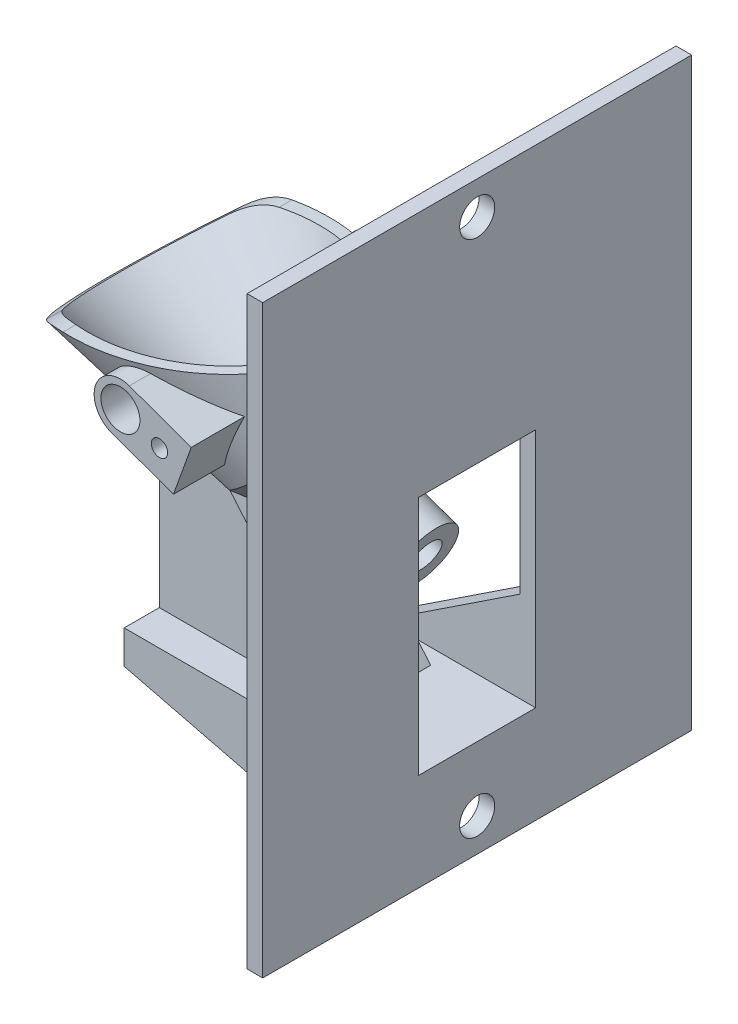
SolidWorks part; units mm, degrees
ref_plane "Front Plane" through (0, 0, 0) normal (0, 0, 1) x (1, 0, 0)
ref_plane "Top Plane" through (0, 0, 0) normal (0, 1, 0) x (1, 0, 0)
ref_plane "Right Plane" through (0, 0, 0) normal (1, 0, 0) x (0, 0, -1)
sketch "Sketch3" plane through (0, 0, 0) normal (0, 0, 1) x (1, 0, 0)
  line L0 (-17.8622, 0) -> (0, 0)
  line L1 (0, 0) -> (-19.1327, 22.8015) construction
  line L2 (-19.1327, 22.8015) -> (-25.9429, 17.0871)
  line L3 (-25.9429, 17.0871) -> (-22.2616, 12.7)
  line L4 (-19.1327, 22.8015) -> (-12.3226, 28.5159)
  line L5 (-12.3226, 28.5159) -> (-8.6414, 24.1288)
  line L6 (-8.6414, 24.1288) -> (-22.2616, 12.7)
  line L7 (-33.7983, 0) -> (-33.7983, 23.2761)
  line L8 (-21.5435, 20.7787) -> (-17.8622, 16.3915)
  line L9 (-12.3226, 28.5159) -> (-12.3226, 0) construction
  line L10 (-33.7983, 0) -> (-33.7983, -4.3404)
  line L11 (-33.7983, -4.3404) -> (0, -4.3404)
  line L12 (0, 0) -> (0, -12.7)
  line L13 (-33.7983, 0) -> (-17.8622, 0)
  line L14 (-24.7754, 18.0667) -> (-9.6156, 0)
  line L15 (-19.1327, 22.8015) -> (-15.4515, 18.4144)
  line L16 (0, 63.5) -> (0, 0)
  line L17 (2.54, 31.3797) -> (0, 31.3797)
  line L18 (2.032, 63.5) -> (2.032, -12.7)
  line L19 (2.032, -12.7) -> (0, -12.7)
  line L20 (-33.7983, -4.3404) -> (0, -12.7)
  line L21 (-17.8622, 0) -> (0, 11.8176)
  line L22 (-53.2486, 32.8521) -> (-15.0089, 35.8964)
  line L23 (2.032, 63.5) -> (0, 63.5)
  line L24 (0, 0) -> (2.54, 0)
  line L25 (-12.3226, 28.5159) -> (0, 38.8558)
  line L26 (-8.6414, 24.1288) -> (0, 31.3797)
  line L27 (-24.7754, 18.0667) -> (-52.0811, 33.8317)
  line L28 (-26.7783, 33.9859) -> (-18.7085, 31.0845)
  line L29 (-53.2486, 32.8521) -> (-25.9429, 17.0871)
  line L30 (-12.3226, 28.5159) -> (-23.1065, 58.1443)
  line L31 (-18.7085, 31.0845) -> (-21.0254, 24.6402)
  line L32 (-13.4901, 27.5363) -> (-24.2739, 57.1647)
  line L33 (-21.0254, 24.6402) -> (-29.0953, 27.5416)
  line L34 (-27.9368, 30.7637) -> (-19.867, 27.8624) construction
  line L36 (-53.2486, 32.8521) -> (-23.1065, 58.1443)
  line L37 (-12.3226, 28.5159) -> (-12.3226, 21.0398)
  circle A0 centre (-27.9368, 30.7637) radius 2.54
  arc A1 (-29.0953, 27.5416) -> (-26.7783, 33.9859) centre (-27.9368, 30.7637) cw
  circle A2 centre (-22.8457, 28.9333) radius 1.0668
  dimension "D7" = 1.524
  dimension "D3" = 1.524
  dimension "D6" = 5.4102
  dimension "D1" = 50
  dimension "D2" = 17.78
  dimension "D4" = 160
  dimension "D5" = 160
revolve "Revolve1" add sketch "Sketch3" angle 360 about L1 region at (-14.921, 23.0591, 0) region at (-19.7155, 46.7478, 0) region at (-14.3401, 31.9267, 0)
extrude "Boss-Extrude1" add sketch "Sketch3<28>" along normal blind 10.16 and the other way blind 10.16 separate body contours L24 L12 L19 L18 | L16 L24 L18 L17 | L18 L23 L16 L17 | L5 L26 L16 L25 | L21 L14 L0 L16 | L21 L0 L14 | L13 L10 L11 L12 L0 | L11 L20 L12 | L6 L5 L4 | L5 L37 L6 region at (-13.3458, 1.1694, 0) region at (-16.8992, -2.1702, 0) region at (-4.7801, 4.3791, 0) region at (1.016, -6.35, 0) region at (1.016, 15.6899, 0) region at (-11.2661, -7.127, 0) region at (-5.2949, 30.8936, 0) region at (1.016, 47.4399, 0) region at (-14.921, 23.0591, 0) region at (-11.0955, 24.5615, 0)
sketch "Sketch3<28>" plane through (0, 0, 0) normal (0, 0, 1) x (1, 0, 0) same geometry as "Sketch3"
extrude "Cut-Extrude1" cut sketch "Sketch3<29>" against normal blind 7.62 and the other way blind 7.62 contours L21 L14 L0 L16 | L21 L0 L14 | L11 L20 L12 | L16 L24 L18 L17 region at (-13.3458, 1.1694, 0) region at (-4.7801, 4.3791, 0) region at (1.016, 15.6899, 0) region at (-11.2661, -7.127, 0)
sketch "Sketch3<29>" plane through (0, 0, 0) normal (0, 0, 1) x (1, 0, 0) same geometry as "Sketch3"
extrude "Boss-Extrude3" add sketch "Sketch3<32>" along normal blind 5.588 and the other way blind 5.588 contours L29 L7 L13 L21 L14 L6 L3 | L21 L0 L14 | L7 L29 L2 L27 | L14 L2 L3 L6 region at (-13.3458, 1.1694, 0) region at (-25.8028, 8.145, 0) region at (-29.572, 20.0283, 0) region at (-23.5185, 15.3834, 0)
sketch "Sketch3<32>" plane through (0, 0, 0) normal (0, 0, 1) x (1, 0, 0) same geometry as "Sketch3"
extrude "Cut-Extrude2" cut sketch "Sketch3<33>" against normal blind 3.556 and the other way blind 3.556 contours L29 L7 L13 L21 L14 L6 L3 | L21 L0 L14 region at (-13.3458, 1.1694, 0) region at (-25.8028, 8.145, 0)
sketch "Sketch3<33>" plane through (0, 0, 0) normal (0, 0, 1) x (1, 0, 0) same geometry as "Sketch3"
extrude "Cut-Extrude3" cut sketch "Sketch3<34>" against normal through all and the other way through all contours L36 L27 L32 | L27 | L32 L30 region at (-52.0204, 33.2454, 0) region at (-31.2803, 41.9558, 0) region at (-19.7155, 46.7478, 0)
sketch "Sketch3<34>" plane through (0, 0, 0) normal (0, 0, 1) x (1, 0, 0) same geometry as "Sketch3"
extrude "Boss-Extrude5" add sketch "Sketch3<39>" along normal blind 16.51 and the other way blind 16.51 contours A1 L33 L31 L28 A2 A0 | A0 | A2 region at (-24.3051, 29.458, 0) region at (-27.9368, 30.7637, 0) region at (-22.8457, 28.9333, 0)
sketch "Sketch3<39>" plane through (0, 0, 0) normal (0, 0, 1) x (1, 0, 0) same geometry as "Sketch3"
extrude "Cut-Extrude8" cut sketch "Sketch3<40>" against normal up to surface and the other way up to surface contours A0 | A1 L33 L31 L28 A2 A0 | A2 region at (-24.3051, 29.458, 0) region at (-27.9368, 30.7637, 0) region at (-22.8457, 28.9333, 0) up to face at (-24.5109, 29.6383, 10.0926) other way up to face at (-24.5109, 29.6383, 10.0926)
sketch "Sketch3<40>" plane through (0, 0, 0) normal (0, 0, 1) x (1, 0, 0) same geometry as "Sketch3"
sketch "Sketch8" plane through (2.032, 0, 0) normal (1, 0, 0) x (0, 0, -1)
  line L0 (0, 0) -> (0, 27.94) construction
  line L1 (0, 0) -> (0, -8.382) construction
  line L2 (0, 31.3797) -> (0, 59.182) construction
  line L3 (-7.62, 31.3797) -> (7.62, 31.3797) construction
  circle A0 centre (0, 27.94) radius 1.778
  circle A1 centre (0, 59.182) radius 2.286
  circle A2 centre (0, -8.382) radius 2.286
  circle A3 centre (0, 27.94) radius 3.048
chamfer "Chamfer1" distance 5.08 angle 45 2 edges at (1.016, 63.5, 10.16) (1.016, 63.5, -10.16)
sketch "Sketch9" plane through (-19.1327, 22.8015, 0) normal (-0.6428, 0.766, 0) x (0.766, 0.6428, 0)
  line L1 (59.7285, 61.802) -> (-65.5702, 61.802)
  line L2 (59.7285, 61.802) -> (59.7285, -72.9851)
  line L3 (59.7285, -72.9851) -> (-65.5702, -72.9851)
  line L4 (-65.5702, 61.802) -> (-65.5702, -72.9851)
  line L5 (59.7285, 61.802) -> (-65.5702, -72.9851) construction
  line L6 (59.7285, -72.9851) -> (-65.5702, 61.802) construction
  point P0 (-2.9209, -5.5916)
extrude "Cut-Extrude15" cut sketch "Sketch9" along normal through all from offset 21.59
fillet "Fillet6" radius 7.62 2 edges at (-39.4322, 33.952, 13.6038) (-39.4322, 33.952, -13.6038)
fillet "Fillet7" radius 10.414 1 edges at (-13.4901, 27.5363, 0)
fillet "Fillet22" radius 5.08 2 edges at (-17.2921, 20.6079, -10.16) (-17.2921, 20.6079, 10.16)
sketch "Sketch10" plane through (0, -4.3404, 0) normal (0, -1, 0) x (1, 0, 0)
  text T0 "<b>KemereLab</b>" font "Century Gothic" height 3.81
extrude "Cut-Extrude17" cut sketch "Sketch10" against normal blind 0.762
ref_plane "Plane3" through (-25.2685, 9.0848, 0) normal (0.941, -0.3383, 0) x (0, 0, -1)
sketch "Sketch7" plane through (-31.2278, -7.4903, 0) normal (0.941, -0.3383, 0) x (-0.3383, -0.941, 0)
  circle A1 centre (-32.5976, 0) radius 2.032
  circle A2 centre (-32.5976, 0) radius 4.064
  ellipse E0 centre (-32.5976, 0) end of major axis (-32.5976, 0.074) minor radius 0.064 construction
extrude "Boss-Extrude8" add sketch "Sketch3<44>" along normal blind 27.94 and the other way blind 27.94 contours L18 L23 L16 L17 | L16 L24 L18 L17 | L24 L12 L19 L18 region at (1.016, -6.35, 0) region at (1.016, 15.6899, 0) region at (1.016, 47.4399, 0)
sketch "Sketch3<44>" plane through (0, 0, 0) normal (0, 0, 1) x (1, 0, 0) same geometry as "Sketch3"
extrude "Cut-Extrude20" cut sketch "Sketch8" against normal up to surface (2.032 mm away) contours A2 | A1 region at (2.032, 59.182, 0) region at (2.032, -8.382, 0) up to face at (0, 35.1178, 0)
extrude "Cut-Extrude21" cut sketch "Sketch3<45>" against normal blind 7.62 and the other way blind 7.62 contours L16 L24 L18 L17 region at (1.016, 15.6899, 0)
sketch "Sketch3<45>" plane through (0, 0, 0) normal (0, 0, 1) x (1, 0, 0) same geometry as "Sketch3"
extrude "Cut-Extrude22" cut sketch "Sketch3<47>" against normal through all and the other way through all contours A0 region at (-27.9368, 30.7637, 0)
sketch "Sketch3<47>" plane through (0, 0, 0) normal (0, 0, 1) x (1, 0, 0) same geometry as "Sketch3"
extrude "Cut-Extrude23" cut sketch "Sketch3<48>" against normal blind 3.81 from surface contours A2 region at (-22.8457, 28.9333, 0) starting at face at (-25.3968, 30.7637, 16.51)
sketch "Sketch3<48>" plane through (0, 0, 0) normal (0, 0, 1) x (1, 0, 0) same geometry as "Sketch3"
extrude "Cut-Extrude24" cut sketch "Sketch3<49>" along normal blind 3.81 from surface contours A2 region at (-22.8457, 28.9333, 0) starting at face at (-25.3968, 30.7637, -16.51)
sketch "Sketch3<49>" plane through (0, 0, 0) normal (0, 0, 1) x (1, 0, 0) same geometry as "Sketch3"
extrude "Boss-Extrude10" add sketch "Sketch7" along normal blind 13.97 from offset 2.54 contours A2 A1 | A1 region at (-20.1991, 23.1849, 0) region at (-18.863, 26.9011, 0)
extrude "Cut-Extrude25" cut sketch "Sketch7<11>" along normal blind 19.558 contours A1 region at (-20.1991, 23.1849, 0)
sketch "Sketch7<11>" plane through (-31.2278, -7.4903, 0) normal (0.941, -0.3383, 0) x (-0.3383, -0.941, 0) same geometry as "Sketch7"
equation "\"0.3.5in\"=0.25"
